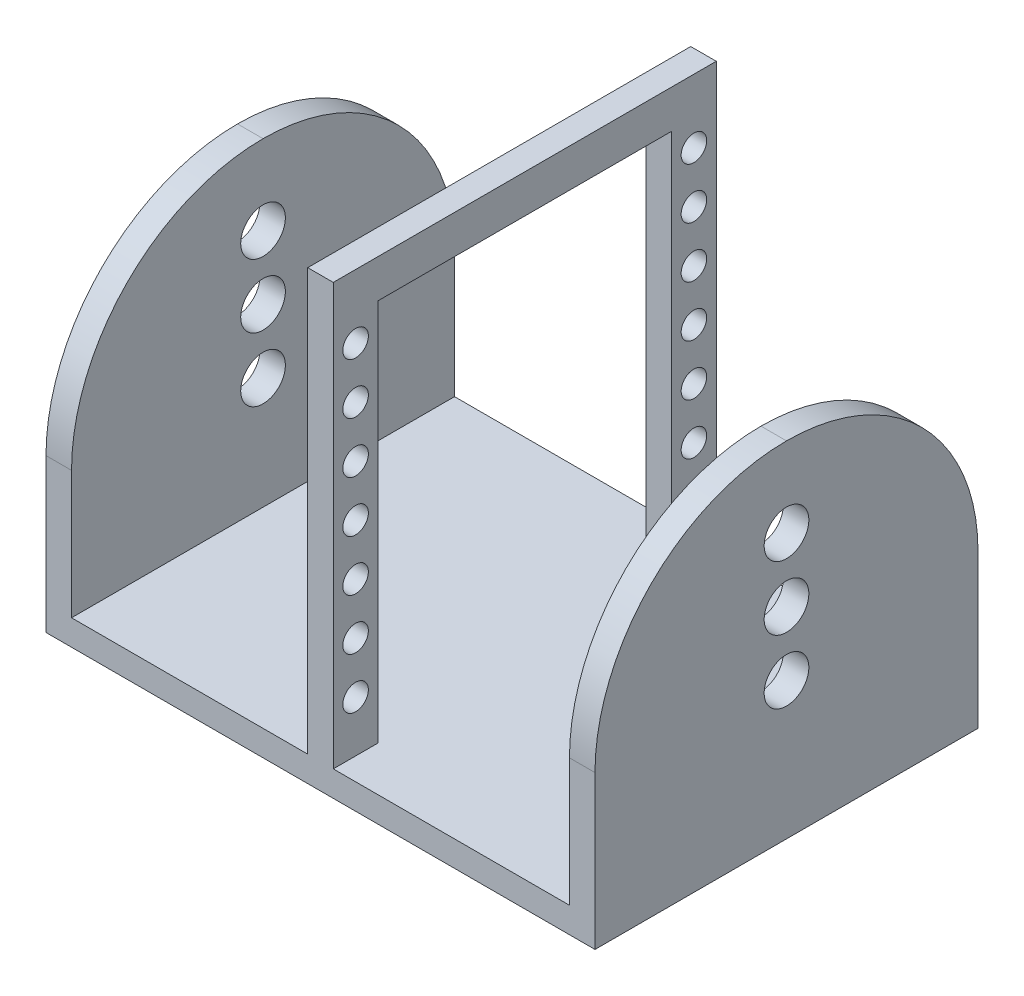
SolidWorks part; units mm, degrees
ref_plane "Front Plane" through (0, 0, 0) normal (0, 0, 1) x (1, 0, 0)
ref_plane "Top Plane" through (0, 0, 0) normal (0, 1, 0) x (1, 0, 0)
ref_plane "Right Plane" through (0, 0, 0) normal (1, 0, 0) x (0, 0, -1)
sketch "Sketch1" plane through (0, 0, 0) normal (0, 1, 0) x (1, 0, 0)
  line L1 (-21.5, 15) -> (21.5, 15)
  line L2 (-21.5, 15) -> (-21.5, -15)
  line L3 (-21.5, -15) -> (21.5, -15)
  line L4 (21.5, 15) -> (21.5, -15)
  line L5 (-21.5, 15) -> (21.5, -15) construction
  line L6 (-21.5, -15) -> (21.5, 15) construction
  point P0 (0, 0)
  dimension "D1" = 43
  dimension "D2" = 30
extrude "Boss-Extrude1" add sketch "Sketch1" along normal blind 2
sketch "Sketch2" plane through (0, 2, 0) normal (0, 1, 0) x (1, 0, 0)
  line L0 (-21.5, -15) -> (21.5, -15) construction
  line L1 (-21.5, 15) -> (-19.5, 15)
  line L2 (-21.5, 15) -> (-21.5, -15)
  line L3 (-21.5, -15) -> (-19.5, -15)
  line L4 (-19.5, 15) -> (-19.5, -15)
  line L6 (21.5, 15) -> (19.5, 15)
  line L7 (21.5, 15) -> (21.5, -15)
  line L8 (21.5, -15) -> (19.5, -15)
  line L9 (19.5, 15) -> (19.5, -15)
  dimension "D1" = 2
  dimension "D2" = 2
extrude "Boss-Extrude2" add sketch "Sketch2" along normal blind 25
fillet "Fillet1" radius 15 4 edges at (20.5, 27, -15) (20.5, 27, 15) (-20.5, 27, 15) (-20.5, 27, -15)
sketch "Sketch3" plane through (-21.5, 0, 0) normal (-1, 0, 0) x (0, 0, 1)
  circle A0 centre (0, 10.7617) radius 1.75
  point P2 (0, 9.3545)
  point P3 (0, 10.7617)
  dimension "D1" = 3.5
extrude "Cut-Extrude1" cut sketch "Sketch3" against normal through all
pattern_linear "LPattern1" count 3 spacing 5 along (0, 1, 0) of "Cut-Extrude1"
sketch "Sketch4" plane through (0, 2, 0) normal (0, 1, 0) x (1, 0, 0)
  line L0 (-19.5, -15) -> (19.5, -15) construction
  line L1 (-1, 15) -> (1, 15)
  line L2 (-1, 15) -> (-1, 11.5)
  line L3 (-1, -15) -> (1, -15)
  line L4 (1, 15) -> (1, 11.5)
  line L5 (-1, 15) -> (1, -15) construction
  line L6 (-1, -15) -> (1, 15) construction
  line L7 (-1, 11.5) -> (1.0957, 11.5)
  line L8 (-1, -11.5) -> (1, -11.5)
  line L9 (-1, -11.5) -> (-1, -15)
  line L10 (1, -11.5) -> (1, -15)
  point P0 (0, 0)
  line M5 (-19.5, -15) -> (19.5, -15)
  line M7 (19.5, 15) -> (-19.5, 15)
  dimension "D1" = 2
  dimension "D2" = 3.5
  dimension "D3" = 3.5
extrude "Boss-Extrude3" add sketch "Sketch4" along normal blind 30 contours L2 L7 L4 M7 | L10 L8 L9 M5 region at (0, 2, -13.25) region at (0, 2, 13.25)
sketch "Sketch5" plane through (0, 32, 0) normal (0, 1, 0) x (1, 0, 0)
  line L1 (-1, 15) -> (1, 15)
  line L2 (-1, 15) -> (-1, -15)
  line L3 (-1, -15) -> (1, -15)
  line L4 (1, 15) -> (1, -15)
extrude "Boss-Extrude4" add sketch "Sketch5" along normal blind 3
sketch "Sketch6" plane through (-1, 0, 0) normal (-1, 0, 0) x (0, 0, 1)
  line L0 (-15, 2) -> (-11.5, 2) construction
  circle A0 centre (-13.25, 6) radius 1
  dimension "D1" = 2
  dimension "D2" = 4
extrude "Cut-Extrude2" cut sketch "Sketch6" against normal blind 3
pattern_linear "LPattern2" count 7 spacing 4 along (0, 1, 0) of "Cut-Extrude2"
mirror "Mirror1" about plane through (0, 0, 0) normal (0, 0, 1) of "LPattern2"
